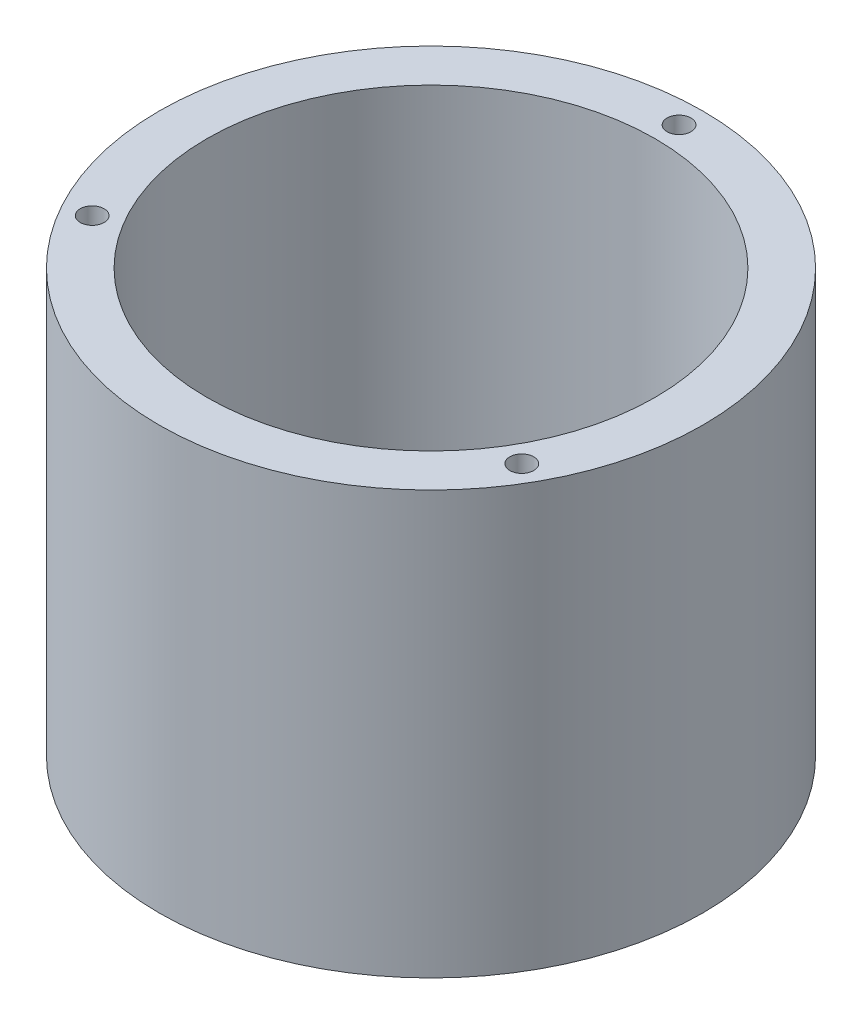
SolidWorks part; units mm, degrees
ref_plane "Front Plane" through (0, 0, 0) normal (0, 0, 1) x (1, 0, 0)
ref_plane "Top Plane" through (0, 0, 0) normal (0, 1, 0) x (1, 0, 0)
ref_plane "Right Plane" through (0, 0, 0) normal (1, 0, 0) x (0, 0, -1)
sketch "Sketch1" plane through (0, 0, 0) normal (0, 1, 0) x (1, 0, 0)
  circle A0 centre (0, 0) radius 45.5
  circle A2 centre (0, 0) radius 33.5
  point P4 (0, 0)
  dimension "D1" = 91
  dimension "D3" = 67
extrude "Boss-Extrude1" add sketch "Sketch1" along normal blind 4
sketch "Sketch2" plane through (0, 4, 0) normal (0, 1, 0) x (1, 0, 0)
  circle A0 centre (0, 0) radius 37.5
  circle A1 centre (0, 0) radius 45.5
  dimension "D1" = 91
  dimension "D2" = 75
extrude "Boss-Extrude2" add sketch "Sketch2" along normal blind 66.7
sketch "Sketch4" plane through (0, 70.7, 0) normal (0, 1, 0) x (1, 0, 0)
  line L0 (0, 0) -> (0, 41.5) construction
  circle A0 centre (0, 41.5) radius 2
  dimension "D1" = 41.5
  dimension "D2" = 4
extrude "Cut-Extrude1" cut sketch "Sketch4" against normal blind 6 contours A0
pattern_circular "CirPattern1" count 3 over 360 about axis through (0, 70.7, 0) along (0, 1, 0) of "Cut-Extrude1"
